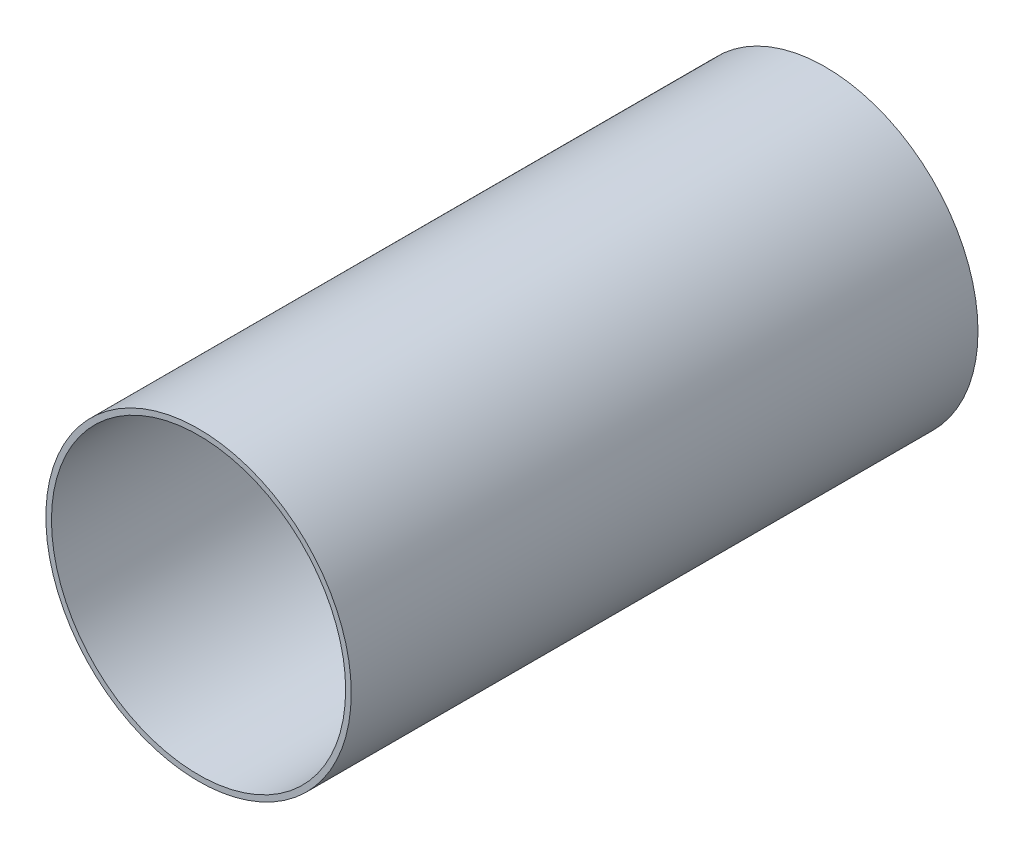
SolidWorks part; units mm, degrees
ref_plane "Front Plane" through (0, 0, 0) normal (0, 0, 1) x (1, 0, 0)
ref_plane "Top Plane" through (0, 0, 0) normal (0, 1, 0) x (1, 0, 0)
ref_plane "Right Plane" through (0, 0, 0) normal (1, 0, 0) x (0, 0, -1)
sketch "Sketch1" plane through (0, 0, 0) normal (0, 0, 1) x (1, 0, 0)
  circle A0 centre (0, 0) radius 49.5046
  circle A1 centre (0, 0) radius 47.6885
  dimension "D1" = 99.0092
  dimension "D2" = 95.377
extrude "Boss-Extrude1" add sketch "Sketch1" along normal blind 203.2
